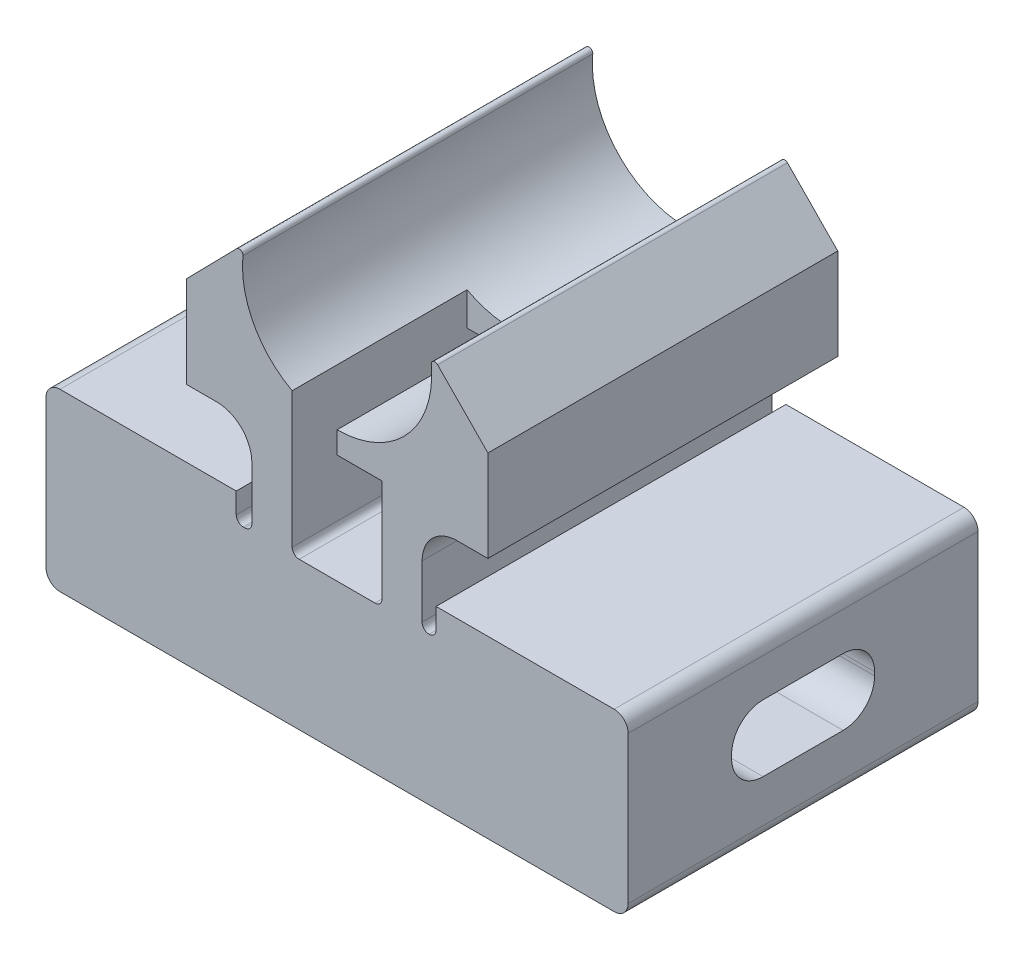
SolidWorks part; units mm, degrees
ref_plane "Front Plane" through (0, 0, 0) normal (0, 0, 1) x (1, 0, 0)
ref_plane "Top Plane" through (0, 0, 0) normal (0, 1, 0) x (1, 0, 0)
ref_plane "Right Plane" through (0, 0, 0) normal (1, 0, 0) x (0, 0, -1)
sketch "Sketch2" plane through (0, 0, 0) normal (0, 0, 1) x (1, 0, 0)
  line L0 (-5.4715, -10.4902) -> (-4.3637, -10.4902)
  line L1 (-3.0937, -11.7602) -> (-3.0937, -12.9378)
  line L2 (-3.0937, -12.9378) -> (-10.5664, -12.9378)
  line L3 (-10.5664, -12.9378) -> (-10.5664, -19.302)
  line L4 (-10.5664, -19.302) -> (10.5664, -19.302)
  line L5 (10.5664, -19.302) -> (10.5664, -12.9378)
  line L6 (10.5664, -12.9378) -> (3.0867, -12.9378)
  line L7 (3.0867, -12.9378) -> (3.0867, -11.7602)
  line L8 (4.3567, -10.4902) -> (5.476, -10.4902)
  line L11 (-3.6504, -5.3147) -> (-5.4715, -7.1736)
  line L12 (3.6502, -5.3139) -> (5.476, -7.1735)
  line L13 (5.476, -10.4902) -> (5.476, -7.1735)
  line L14 (-5.4715, -10.4902) -> (-5.4715, -7.1736)
  arc A0 (3.0867, -11.7602) -> (4.3567, -10.4902) centre (4.3567, -11.7602) cw
  arc A1 (-4.3637, -10.4902) -> (-3.0937, -11.7602) centre (-4.3637, -11.7602) cw
  arc A2 (-3.4187, -5.4224) -> (3.4186, -5.4217) centre (0, -5.7477) ccw
  arc A3 (-1.6181, -4.4958) -> (-3.8632, -5.4257) centre (-1.6181, -7.6708) ccw construction
  arc A4 (3.8632, -5.4257) -> (1.6181, -4.4958) centre (1.6181, -7.6708) ccw construction
  arc A5 (-3.4187, -5.4224) -> (-3.6504, -5.3147) centre (-3.5536, -5.4095) ccw
  arc A6 (3.4186, -5.4217) -> (3.6502, -5.3139) centre (3.5535, -5.4088) cw
  point P0 (-5.4715, -7.1736)
  point P27 (-3.3546, -5.0127)
  point P30 (3.3546, -5.0127)
  dimension "D1" = 1.27
  dimension "D2" = 0.1355
  dimension "D3" = 0.1355
extrude "Boss-Extrude9" add sketch "Sketch2" along normal mid plane 12.7
sketch "Sketch4" plane through (0, 0, 6.35) normal (0, 0, 1) x (1, 0, 0)
  line L1 (-1.6308, -13.9408) -> (1.6308, -13.9408)
  line L2 (-1.6308, -13.9408) -> (-1.6308, -9.9754)
  line L3 (-1.6308, -9.9754) -> (1.6308, -9.9754)
  line L4 (1.6308, -13.9408) -> (1.6308, -9.9754)
  line L5 (-1.6308, -13.9408) -> (1.6308, -9.9754) construction
  line L6 (-1.6308, -9.9754) -> (1.6308, -13.9408) construction
  point P0 (0, -11.9581)
extrude "Cut-Extrude2" cut sketch "Sketch4" against normal through all
sketch "Sketch5" plane through (0, 0, 6.35) normal (0, 0, 1) x (1, 0, 0)
  line L0 (-1.6308, -9.9754) -> (0, -9.9754)
  line L1 (-1.6308, -9.9754) -> (-1.6308, -8.7082)
  line L2 (0, -9.9754) -> (0, -8.7082)
  line L3 (-1.6308, -8.7082) -> (0, -8.7082)
  line L4 (1.6308, -9.9754) -> (-1.6308, -9.9754) construction
extrude "Cut-Extrude6" cut sketch "Sketch5" against normal mid plane 12.7
sketch "Sketch6" plane through (0, 0, -6.35) normal (0, 0, -1) x (-1, 0, 0)
  line L0 (-1.6308, -9.9754) -> (0, -9.9754)
  line L1 (-1.6308, -9.9754) -> (-1.6308, -8.7279)
  line L2 (0, -9.9754) -> (0, -8.7279)
  line L3 (-1.6308, -8.7279) -> (0, -8.7279)
extrude "Cut-Extrude7" cut sketch "Sketch6" against normal mid plane 12.954
sketch "Sketch8" plane through (0, 0, 0) normal (0, 0, 1) x (1, 0, 0)
  line L0 (-3.0937, -12.9378) -> (-3.0937, -13.9408)
  line L1 (-3.0937, -12.9378) -> (-3.6606, -12.9378)
  line L2 (-3.0937, -13.9408) -> (-3.6606, -13.9408)
  line L3 (-3.6606, -12.9378) -> (-3.6606, -13.9408)
extrude "Cut-Extrude9" cut sketch "Sketch8" against normal through all both and the other way through all
sketch "Sketch9" plane through (0, 0, 6.35) normal (0, 0, 1) x (1, 0, 0)
  line L0 (3.0867, -12.9378) -> (3.0867, -13.9408)
  line L1 (3.0867, -12.9378) -> (3.5947, -12.9378)
  line L2 (3.0867, -13.9408) -> (3.5947, -13.9408)
  line L3 (3.5947, -12.9378) -> (3.5947, -13.9408)
extrude "Cut-Extrude10" cut sketch "Sketch9" against normal through all both and the other way through all
fillet "Fillet1" radius 0.254 1 edges at (-3.0937, -13.9408, 0)
fillet "Fillet2" radius 0.254 1 edges at (-3.6606, -13.9408, 0)
fillet "Fillet3" radius 0.254 4 edges at (-1.6308, -13.9408, 0) (1.6308, -13.9408, 0) (3.5947, -13.9408, 0) (3.0867, -13.9408, 0)
fillet "Fillet4" radius 0.508 1 edges at (-10.5664, -12.9378, 0)
fillet "Fillet5" radius 0.508 3 edges at (10.5664, -12.9378, 0) (10.5664, -19.302, 0) (-10.5664, -19.302, 0)
sketch "Sketch11" plane through (-10.5664, 0, 0) normal (-1, 0, 0) x (0, 0, 1)
  line L1 (-2.5952, -14.8365) -> (2.5952, -14.8365)
  line L2 (-2.5952, -14.8365) -> (-2.5952, -17.2517)
  line L3 (-2.5952, -17.2517) -> (2.5952, -17.2517)
  line L4 (2.5952, -14.8365) -> (2.5952, -17.2517)
  line L5 (-2.5952, -14.8365) -> (2.5952, -17.2517) construction
  line L6 (-2.5952, -17.2517) -> (2.5952, -14.8365) construction
  point P0 (0, -16.0441)
extrude "Cut-Extrude11" cut sketch "Sketch11" against normal through all
fillet "Fillet6" radius 1.143 4 edges at (0, -14.8365, -2.5952) (0, -17.2517, -2.5952) (0, -17.2517, 2.5952) (0, -14.8365, 2.5952)
